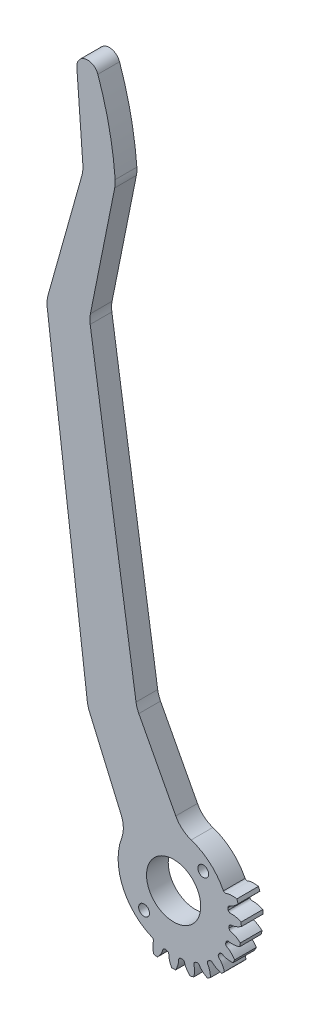
SolidWorks part; units mm, degrees
material "Thornel Mat VMA"
ref_plane "前视基准面" through (0, 0, 0) normal (0, 0, 1) x (1, 0, 0)
ref_plane "上视基准面" through (0, 0, 0) normal (0, 1, 0) x (1, 0, 0)
ref_plane "右视基准面" through (0, 0, 0) normal (1, 0, 0) x (0, 0, -1)
sketch "草图1" plane through (0, 0, 0) normal (0, 0, 1) x (1, 0, 0)
  circle A0 centre (0, 0) radius 12.5
extrude "凸台-拉伸1" add sketch "草图1" along normal blind 4
ref_axis "基准轴1" through (0, 0, 4) along (0, 0, -1)
sketch "草图2" plane through (0, 0, 0) normal (0, 0, 1) x (1, 0, 0)
  line L0 (0, 0) -> (0, 12.5) construction
  circle A0 centre (0, 0) radius 12.5 construction
  arc A1 (0.1814, 10.2484) -> (-0.1814, 10.2484) centre (0, 0) ccw
  arc A2 (3.1817, 14.1862) -> (-3.1817, 14.1862) centre (0, 0) ccw
  spline S0 degree 3 poles (0.1814, 10.2484) (0.5777, 10.3668) (0.5438, 10.6338) (0.5929, 10.8972) (0.5995, 10.9289) (0.6077, 10.9648) (0.6176, 11.0046) (0.6294, 11.0484) (0.6433, 11.0961) (0.6595, 11.1477) (0.6781, 11.203) (0.6992, 11.262) (0.723, 11.3247) (0.7498, 11.3908) (0.7795, 11.4604) (0.8124, 11.5333) (0.8485, 11.6094) (0.8882, 11.6887) (0.9314, 11.7709) (0.9783, 11.8561) (1.0291, 11.9441) (1.0839, 12.0347) (1.1428, 12.1279) (1.2059, 12.2235) (1.2734, 12.3214) (1.3454, 12.4214) (1.4219, 12.5234) (1.5031, 12.6273) (1.5891, 12.7328) (1.68, 12.84) (1.7759, 12.9485) (1.8768, 13.0583) (1.9829, 13.1691) (2.0943, 13.2809) (2.211, 13.3934) (2.3331, 13.5065) (2.4606, 13.62) (2.5937, 13.7338) (2.7324, 13.8476) (2.9271, 14.001) (3.0783, 14.1128) (3.1817, 14.1862) knots 0 0 0 0 0.147387 0.15296 0.159389 0.166677 0.174821 0.183823 0.193683 0.204399 0.215973 0.228404 0.241693 0.255839 0.270842 0.286703 0.303421 0.320996 0.339428 0.358718 0.378866 0.39987 0.421732 0.444451 0.468028 0.492462 0.517753 0.543901 0.570907 0.59877 0.627491 0.657069 0.687504 0.718796 0.750946 0.783953 0.817818 0.85254 0.888119 0.924555 1 1 1 1
  spline S1 degree 3 poles (-0.1814, 10.2484) (-0.5777, 10.3668) (-0.5438, 10.6338) (-0.5929, 10.8972) (-0.5995, 10.9289) (-0.6077, 10.9648) (-0.6176, 11.0046) (-0.6294, 11.0484) (-0.6433, 11.0961) (-0.6595, 11.1477) (-0.6781, 11.203) (-0.6992, 11.262) (-0.723, 11.3247) (-0.7498, 11.3908) (-0.7795, 11.4604) (-0.8124, 11.5333) (-0.8485, 11.6094) (-0.8882, 11.6887) (-0.9314, 11.7709) (-0.9783, 11.8561) (-1.0291, 11.9441) (-1.0839, 12.0347) (-1.1428, 12.1279) (-1.2059, 12.2235) (-1.2734, 12.3214) (-1.3454, 12.4214) (-1.4219, 12.5234) (-1.5031, 12.6273) (-1.5891, 12.7328) (-1.68, 12.84) (-1.7759, 12.9485) (-1.8768, 13.0583) (-1.9829, 13.1691) (-2.0943, 13.2809) (-2.211, 13.3934) (-2.3331, 13.5065) (-2.4606, 13.62) (-2.5937, 13.7338) (-2.7324, 13.8476) (-2.9271, 14.001) (-3.0783, 14.1128) (-3.1817, 14.1862) knots 0 0 0 0 0.147387 0.15296 0.159389 0.166677 0.174821 0.183823 0.193683 0.204399 0.215973 0.228404 0.241693 0.255839 0.270842 0.286703 0.303421 0.320996 0.339428 0.358718 0.378866 0.39987 0.421732 0.444451 0.468028 0.492462 0.517753 0.543901 0.570907 0.59877 0.627491 0.657069 0.687504 0.718796 0.750946 0.783953 0.817818 0.85254 0.888119 0.924555 1 1 1 1
extrude "切除-拉伸1" cut sketch "草图2" along normal through all
pattern_circular "阵列(圆周)1" count 23 every 15.652 about axis through (0, 0, 4) along (0, 0, -1) of "切除-拉伸1"
sketch "草图3" plane through (0, 0, 0) normal (0, 0, 1) x (1, 0, 0)
  circle A0 centre (0, 0) radius 11.5 construction
  dimension "Dn" = 23
sketch "草图4" plane through (0, 0, 4) normal (0, 0, 1) x (1, 0, 0)
  line L0 (0, 0) -> (3.9627, 0.5447) construction
  line L1 (3.9627, 0.5447) -> (-10.7431, 107.5388) construction
  line L2 (0, 0) -> (-11.3296, 23.6778) construction
  line L3 (-11.3296, 23.6778) -> (-19.4995, 83.119) construction
  line L4 (-19.4995, 83.119) -> (-13.7151, 107.1303) construction
  line L5 (-15.5368, 83.6637) -> (-10.7431, 107.5388)
  line L6 (-23.4623, 82.5743) -> (-15.5368, 83.6637) construction
  line L7 (-15.8399, 21.5197) -> (-6.8193, 25.836) construction
  line L8 (-5.5074, -2.3809) -> (-15.8399, 21.5197)
  line L9 (5.3093, 2.7948) -> (-6.8193, 25.836)
  line L10 (-6.8193, 25.836) -> (-15.5368, 83.6637)
  line L11 (-15.8399, 21.5197) -> (-23.4623, 82.5743)
  line L12 (-23.4623, 82.5743) -> (-16.6872, 106.7218)
  line L13 (-16.6872, 106.7218) -> (-17.867, 122.6782)
  arc A0 (-5.5074, -2.3809) -> (5.3093, 2.7948) centre (0, 0) ccw
  arc A1 (-13.9846, 123.4862) -> (-17.867, 122.6782) centre (-15.8724, 122.8257) ccw
  arc A3 (-10.7431, 107.5388) -> (-13.9846, 123.4862) centre (-70.6183, 103.6715) ccw
extrude "凸台-拉伸2" add sketch "草图4" against normal blind 4 contours L5 A3 A1 L13 L12 L11 L8 A0 L9 L10 region at (-12.1203, 50.333, 4)
sketch "草图5" plane through (0, 0, 4) normal (0, 0, 1) x (1, 0, 0)
  line L1 (-4.0836, -9.4014) -> (-5.976, -13.7582)
  line L3 (9.1828, 4.5539) -> (13.4383, 6.6642)
  line L4 (-8.8051, 5.2472) -> (-10.9627, 10.2381)
  line L5 (-9.7628, 7.4625) -> (-15.8399, 21.5197) construction
  line L6 (1.4384, 10.1486) -> (-1.0943, 14.96)
  line L10 (0.7653, 11.4271) -> (-6.8193, 25.836) construction
  arc A0 (9.1828, 4.5539) -> (1.4384, 10.1486) centre (0, 0) ccw
  arc A1 (13.4383, 6.6642) -> (-1.0943, 14.96) centre (0, 0) ccw
  arc A2 (-10.9627, 10.2381) -> (-5.976, -13.7582) centre (0, 0) ccw
  arc A3 (-8.8051, 5.2472) -> (-4.0836, -9.4014) centre (0, 0) ccw
  arc A4 (-4.2493, -9.3277) -> (-3.9166, -9.4722) centre (0, 0) ccw construction
  dimension "D1" = 30
extrude "切除-拉伸2" cut sketch "草图5" against normal blind 10
fillet "圆角1" radius 5 8 edges at (-16.6872, 106.7218, 2) (-10.7431, 107.5388, 2) (-15.5368, 83.6637, 2) (-23.4623, 82.5743, 2) (-15.8399, 21.5197, 2) (-6.8193, 25.836, 2) (1.4384, 10.1486, 2) (-8.8051, 5.2472, 2)
sketch "草图6" plane through (0, 0, 0) normal (0, 0, -1) x (-1, 0, 0)
  circle A0 centre (0, 0) radius 5
  dimension "D1" = 10
extrude "切除-拉伸3" cut sketch "草图6" against normal blind 10
sketch "草图7" plane through (0, 0, 4) normal (0, 0, 1) x (1, 0, 0)
  line L0 (-5.4604, -5.8467) -> (5.4604, 5.8467) construction
  line L1 (9.1354, -8.5319) -> (0, 0) construction
  circle A0 centre (0, 0) radius 8 construction
  circle A1 centre (-5.4604, -5.8467) radius 1
  circle A2 centre (5.4604, 5.8467) radius 1
  arc A3 (8.8896, -8.7878) -> (9.3739, -8.2692) centre (0, 0) ccw construction
  dimension "D1" = 16
  dimension "D2" = 2
  dimension "D3" = 2
extrude "切除-拉伸4" cut sketch "草图7" against normal blind 10
